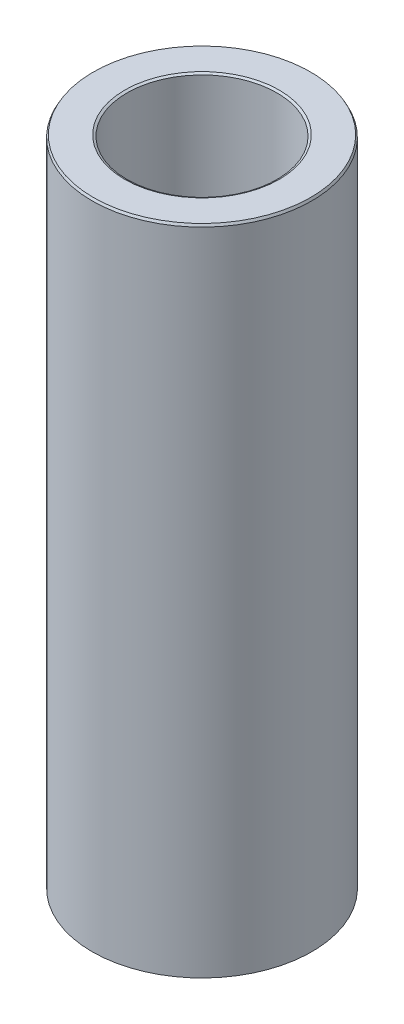
SolidWorks part; units mm, degrees
ref_plane "Front Plane" through (0, 0, 0) normal (0, 0, 1) x (1, 0, 0)
ref_plane "Top Plane" through (0, 0, 0) normal (0, 1, 0) x (1, 0, 0)
ref_plane "Right Plane" through (0, 0, 0) normal (1, 0, 0) x (0, 0, -1)
sketch "Sketch1" plane through (0, 0, 0) normal (0, 1, 0) x (1, 0, 0)
  circle A0 centre (0, 0) radius 47.5
  dimension "SLEEVE_OD" = 95
extrude "Boss-Extrude1" add sketch "Sketch1" along normal blind 282.5443
sketch "Sketch2" plane through (0, 0, 0) normal (0, 1, 0) x (1, 0, 0)
  circle A0 centre (0, 0) radius 32.4189
  dimension "BORE_D" = 64.8378
extrude "Cut-Extrude1" cut sketch "Sketch2" along normal through all
chamfer "Chamfer1" distance 1.0003 angle 28.17 4 edges at (0, 282.5443, 32.4189) (0, 0, 32.4189) (0, 0, 47.5) (0, 282.5443, 47.5) first distance on face at (0, 282.5443, 32.4189) first distance on face at (0, 0, 32.4189) first distance on face at (0, 282.5443, 47.5)
